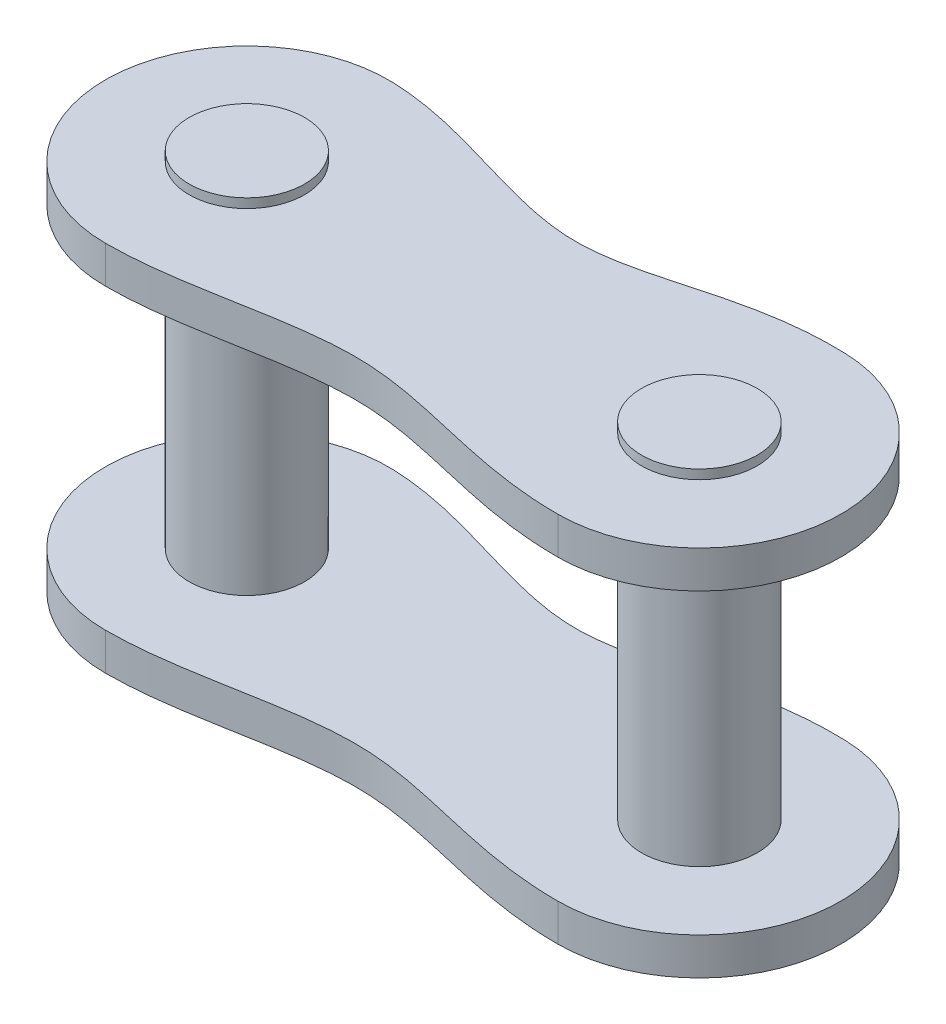
SolidWorks part; units mm, degrees
material "铸造合金钢"
ref_plane "前视基准面" through (0, 0, 0) normal (0, 0, 1) x (1, 0, 0)
ref_plane "上视基准面" through (0, 0, 0) normal (0, 1, 0) x (1, 0, 0)
ref_plane "右视基准面" through (0, 0, 0) normal (1, 0, 0) x (0, 0, -1)
sketch "草图1" plane through (0, 0, 0) normal (0, 1, 0) x (1, 0, 0)
  circle A0 centre (-56.2357, 24.7329) radius 3.8
  circle A1 centre (-43.8557, 24.5057) radius 3.8
  circle A7 centre (-56.2357, 24.7329) radius 1.55
  circle A8 centre (-43.8557, 24.5057) radius 1.5539
  spline S0 degree 3 poles (-56.0931, 28.5302) (-53.9426, 28.4494) (-49.7686, 26.1495) (-46.434, 28.3981) (-43.723, 28.3034) knots 0 0 0 0 0.490575 1 1 1 1
  spline S1 degree 3 poles (-56.2357, 20.9329) (-54.1058, 20.9329) (-49.896, 22.4778) (-46.2524, 20.7057) (-43.8557, 20.7057) knots 0 0 0 0 0.49851 1 1 1 1
sketch "草图4" plane through (0, 0, 0) normal (0, 1, 0) x (1, 0, 0)
  circle A0 centre (-56.2357, 24.7329) radius 1.55
  circle A1 centre (-43.8557, 24.5057) radius 1.5539
sketch "草图6" plane through (0, 0, 0) normal (0, 1, 0) x (1, 0, 0)
  circle A0 centre (-43.8557, 24.5057) radius 1.5539 construction
  circle A1 centre (-43.8557, 24.5057) radius 3.8 construction
  circle A2 centre (-56.2357, 24.7329) radius 3.8 construction
  circle A3 centre (-56.2357, 24.7329) radius 1.55 construction
  circle A4 centre (-43.8557, 24.5057) radius 1.5539
  circle A5 centre (-43.8557, 24.5057) radius 3.8
  circle A6 centre (-56.2357, 24.7329) radius 3.8
  circle A7 centre (-56.2357, 24.7329) radius 1.55
  circle A8 centre (-56.2357, 24.7329) radius 1.7
  circle A9 centre (-43.8557, 24.5057) radius 1.7039
  spline S0 degree 3 poles (38.0208, 3018.5861) (-123.8084, -113.6518) (-29.2173, 151.338) (-23.2118, -102.6478) (1232.8358, 2734.4178) knots -5.921037 -5.921037 -5.921037 -5.921037 0.49851 6.587332 6.587332 6.587332 6.587332 only from (-56.2357, 20.9329) to (-43.8557, 20.7057) construction
  spline S1 degree 3 poles (-38.5058, -2970.5982) (-121.075, 178.4888) (-24.6821, -115.8306) (-34.009, 162.7507) (1461.0641, -2565.8142) knots -5.25994 -5.25994 -5.25994 -5.25994 0.490575 5.962914 5.962914 5.962914 5.962914 only from (-56.0931, 28.5302) to (-43.723, 28.3034) construction
  spline S2 degree 3 poles (-56.2357, 20.9329) (-54.1058, 20.9329) (-49.896, 22.4778) (-46.2524, 20.7057) (-43.8557, 20.7057) knots 0 0 0 0 0.49851 1 1 1 1
  spline S3 degree 3 poles (-56.0931, 28.5302) (-53.9426, 28.4494) (-49.7686, 26.1495) (-46.434, 28.3981) (-43.723, 28.3034) knots 0 0 0 0 0.490575 1 1 1 1
  dimension "D1" = 0.15
  dimension "D2" = 0.15
extrude "凸台-拉伸7" add sketch "草图1" along normal blind 1 from offset 4 contours A0 A7 | A0 S1 A1 S0 | A1 A8 region at (-41.1995, 0, -27.0707) region at (-53.6247, 0, -22.1219) region at (-50.0101, 0, -24.484)
extrude "凸台-拉伸11" add sketch "草图6" against normal blind 1 from offset 4 separate body contours S3 A6 S2 A5 | A6 A8 | A8 A7 | A5 A9 | A9 A4 region at (-53.5762, 0, -27.2944) region at (-50.0101, 0, -24.484) region at (-41.2447, 0, -21.8947) region at (-57.8876, 0, -24.7329) region at (-45.5114, 0, -24.5057) offset against normal yes
extrude "凸台-拉伸12" add sketch "草图4" along normal mid plane 10.5 contours A0
extrude "凸台-拉伸13" add sketch "草图4<5>" along normal mid plane 10.5
sketch "草图4<5>" plane through (0, 0, 0) normal (0, 1, 0) x (1, 0, 0) same geometry as "草图4"
sketch "草图7" plane through (0, 0, 0) normal (0, 0, 1) x (1, 0, 0)
  line L0 (-56.2357, 5) -> (-43.8557, 5)
